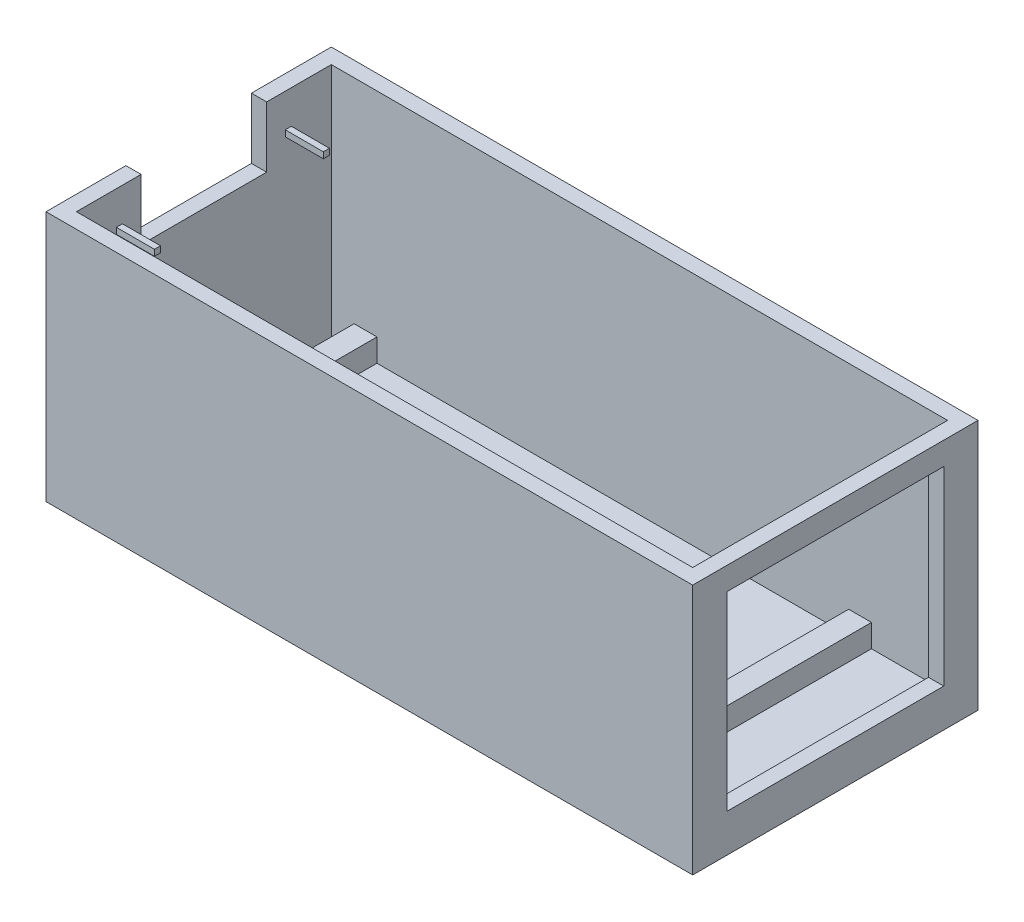
SolidWorks part; units mm, degrees
ref_plane "Front Plane" through (0, 0, 0) normal (0, 0, 1) x (1, 0, 0)
ref_plane "Top Plane" through (0, 0, 0) normal (0, 1, 0) x (1, 0, 0)
ref_plane "Right Plane" through (0, 0, 0) normal (1, 0, 0) x (0, 0, -1)
sketch "Sketch1" plane through (0, 0, 0) normal (0, 1, 0) x (1, 0, 0)
  line L1 (0, 0) -> (85, 0)
  line L2 (0, 0) -> (0, 37.5)
  line L3 (0, 37.5) -> (85, 37.5)
  line L4 (85, 0) -> (85, 37.5)
  dimension "D1" = 85
  dimension "D2" = 37.5
extrude "Boss-Extrude2" add sketch "Sketch1" along normal blind 2 contours L2 L3 L4 L1
sketch "Sketch2" plane through (0, 2, 0) normal (0, 1, 0) x (1, 0, 0)
  line L0 (0, 37.5) -> (85, 37.5) construction
  line L1 (5, 37.5) -> (8, 37.5)
  line L2 (5, 37.5) -> (5, 0)
  line L3 (5, 0) -> (8, 0)
  line L4 (8, 37.5) -> (8, 0)
  line L5 (0, 0) -> (85, 0) construction
  line L6 (0, 0) -> (0, 37.5) construction
  line L7 (70, 37.5) -> (73, 37.5)
  line L8 (70, 37.5) -> (70, 0)
  line L9 (70, 0) -> (73, 0)
  line L10 (73, 37.5) -> (73, 0)
  line L11 (85, 0) -> (85, 37.5) construction
  dimension "D1" = 3
  dimension "D2" = 5
  dimension "D3" = 12
  dimension "D4" = 3
extrude "Boss-Extrude4" add sketch "Sketch2" along normal blind 3
sketch "Sketch4" plane through (0, 2, 0) normal (0, 1, 0) x (1, 0, 0)
  line L0 (8, 37.5) -> (5, 37.5) construction
  line L1 (8, 37.5) -> (70, 37.5) construction
  line L2 (73, 37.5) -> (70, 37.5) construction
  line L3 (73, 37.5) -> (85, 37.5) construction
  line L4 (85, 0) -> (85, 37.5) construction
  line L5 (73, 0) -> (85, 0) construction
  line L6 (70, 0) -> (73, 0) construction
  line L7 (8, 0) -> (70, 0) construction
  line L8 (5, 0) -> (8, 0) construction
  line L9 (0, 0) -> (5, 0) construction
  line L10 (0, 0) -> (0, 37.5) construction
  line L11 (0, 37.5) -> (5, 37.5) construction
  line L12 (8, 37.5) -> (5, 37.5)
  line L13 (8, 37.5) -> (70, 37.5)
  line L14 (73, 37.5) -> (70, 37.5)
  line L15 (73, 37.5) -> (85, 37.5)
  line L16 (85, 0) -> (85, 37.5)
  line L17 (73, 0) -> (85, 0)
  line L18 (70, 0) -> (73, 0)
  line L19 (8, 0) -> (70, 0)
  line L20 (5, 0) -> (8, 0)
  line L21 (0, 0) -> (5, 0)
  line L22 (0, 0) -> (0, 37.5)
  line L23 (0, 37.5) -> (5, 37.5)
  line L24 (2, 2) -> (2, 35.5)
  line L25 (2, 35.5) -> (5, 35.5)
  line L26 (8, 35.5) -> (5, 35.5)
  line L27 (8, 35.5) -> (70, 35.5)
  line L28 (73, 35.5) -> (70, 35.5)
  line L29 (73, 35.5) -> (83, 35.5)
  line L30 (83, 2) -> (83, 35.5)
  line L31 (73, 2) -> (83, 2)
  line L32 (70, 2) -> (73, 2)
  line L33 (8, 2) -> (70, 2)
  line L34 (5, 2) -> (8, 2)
  line L35 (2, 2) -> (5, 2)
  dimension "D1" = 2
extrude "Boss-Extrude5" add sketch "Sketch4" along normal blind 31
sketch "Sketch6" plane through (0, 0, 0) normal (-1, 0, 0) x (0, 0, 1)
  line L0 (-37.5, 33) -> (0, 33) construction
  line L1 (-27, 33) -> (-10.5, 33)
  line L2 (-27, 33) -> (-27, 25)
  line L3 (-27, 25) -> (-10.5, 25)
  line L4 (-10.5, 33) -> (-10.5, 25)
  line L5 (-18.75, 0) -> (-18.75, 33.7611) construction
  line L6 (0, 0) -> (-37.5, 0) construction
  dimension "D1" = 16.5
  dimension "D2" = 8
extrude "Cut-Extrude1" cut sketch "Sketch6" against normal blind 2
sketch "Sketch7" plane through (85, 0, 0) normal (1, 0, 0) x (0, 0, -1)
  line L0 (0, 0) -> (37.5, 0) construction
  line L1 (4.5, 30) -> (33, 30)
  line L2 (4.5, 30) -> (4.5, 5)
  line L3 (4.5, 5) -> (33, 5)
  line L4 (33, 30) -> (33, 5)
  line L5 (18.75, 0) -> (18.75, 34.1605) construction
  dimension "D1" = 25
  dimension "D2" = 28.5
  dimension "D3" = 5
extrude "Cut-Extrude2" cut sketch "Sketch7" against normal blind 2
sketch "Sketch8" plane through (2, 0, 0) normal (1, 0, 0) x (0, 0, -1)
  line L0 (10.5, 33) -> (2, 33) construction
  line L1 (7.25, 28.6) -> (8.05, 28.6)
  line L2 (7.25, 28.6) -> (7.25, 27.8)
  line L3 (7.25, 27.8) -> (8.05, 27.8)
  line L4 (8.05, 28.6) -> (8.05, 27.8)
  line L5 (10.5, 25) -> (10.5, 33) construction
  line L6 (18.75, 25) -> (18.75, 37.7153) construction
  line L7 (27, 25) -> (10.5, 25) construction
  line L8 (30.25, 28.6) -> (30.25, 27.8)
  line L9 (30.25, 28.6) -> (29.45, 28.6)
  line L10 (29.45, 28.6) -> (29.45, 27.8)
  line L11 (30.25, 27.8) -> (29.45, 27.8)
  point P8 (7.25, 28.2)
  point P9 (8.05, 28.2)
  point P14 (7.65, 27.8)
  point P19 (29.85, 27.8)
  dimension "D1" = 4.4
  dimension "D2" = 2.45
  dimension "D3" = 0.8
  dimension "D4" = 0.8
extrude "Boss-Extrude6" add sketch "Sketch8" along normal blind 5
sketch "Sketch9" plane through (0, 0, -37.5) normal (0, 0, -1) x (-1, 0, 0)
  line L0 (-85, 33) -> (-85, 0) construction
  line L1 (-73, 27) -> (-38, 27)
  line L2 (-73, 27) -> (-73, 25)
  line L3 (-73, 25) -> (-38, 25)
  line L4 (-38, 27) -> (-38, 25)
  line L5 (-73, 6) -> (-38, 6)
  line L6 (-73, 6) -> (-73, 4)
  line L7 (-73, 4) -> (-38, 4)
  line L8 (-38, 6) -> (-38, 4)
  line L10 (-85, 33) -> (0, 33) construction
  point P8 (-38, 5)
  dimension "D1" = 2
  dimension "D2" = 2
  dimension "D3" = 35
  dimension "D4" = 35
  dimension "D5" = 12
  dimension "D6" = 12
  dimension "D7" = 19
  dimension "D8" = 6
extrude "Boss-Extrude7" add sketch "Sketch9" along normal blind 2.4
